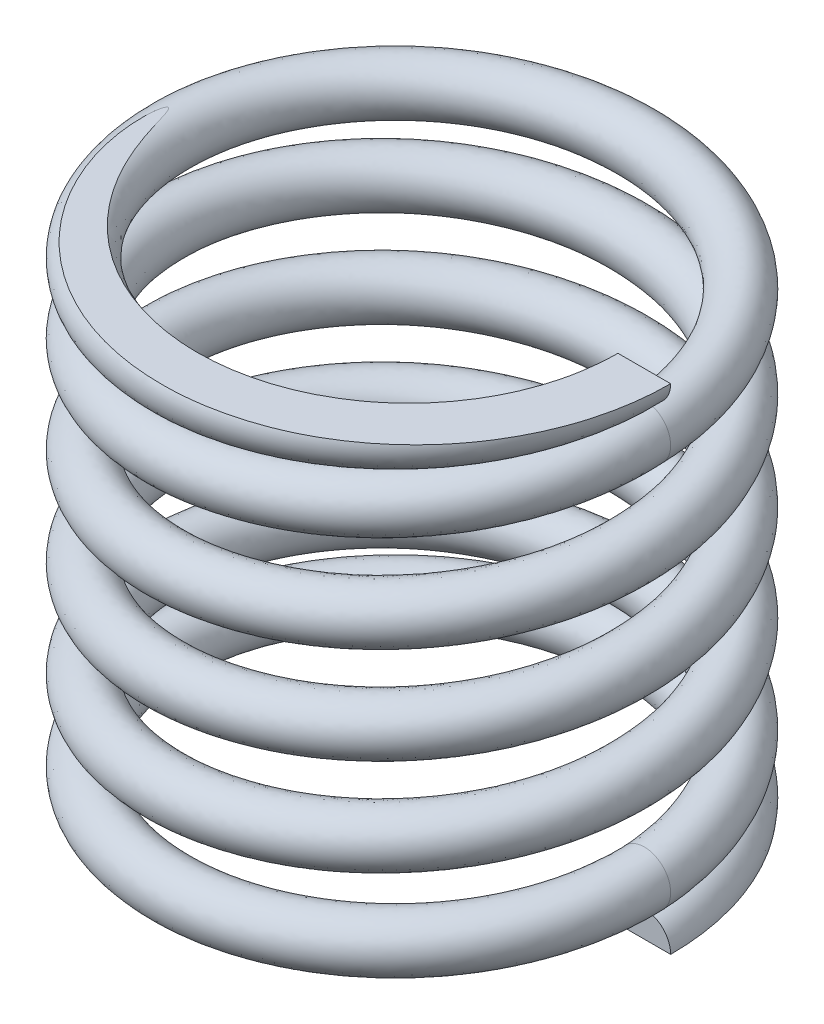
SolidWorks part; units mm, degrees
material "AISI Type 316L stainless steel"
ref_plane "Front" through (0, 0, 0) normal (0, 0, 1) x (1, 0, 0)
ref_plane "Top" through (0, 0, 0) normal (0, 1, 0) x (1, 0, 0)
ref_plane "Right" through (0, 0, 0) normal (1, 0, 0) x (0, 0, -1)
sketch "Sketch1" plane through (0, 0, 0) normal (0, 0, 1) x (1, 0, 0)
  line L0 (7.0499, 15) -> (7.0499, 14.1999) construction
  line L1 (0, 0) -> (7.0499, 0) construction
  line L2 (0, 0) -> (0, 15) construction
  line L3 (0, 15) -> (7.0499, 15) construction
  line L4 (7.0499, 14.1999) -> (7.0499, 14.1745) construction
  line L5 (7.0499, 14.1745) -> (7.0499, 12.5743) construction
  line L6 (7.0499, 12.5743) -> (7.0499, 2.4257) construction
  line L7 (7.0499, 2.4257) -> (7.0499, 0.8255) construction
  line L8 (7.0499, 0.8255) -> (7.0499, 0.8001) construction
  line L9 (7.0499, 0.8001) -> (7.0499, 0) construction
  line L10 (7.0499, 0) -> (7.85, 0) construction
  line L11 (7.0499, 1.6256) -> (7.85, 1.6256) construction
  line L12 (7.0499, 15) -> (7.85, 15) construction
  line L13 (7.0499, 15) -> (7.0499, 15.8001) construction
  line L14 (7.0499, 0) -> (7.0499, -0.8001) construction
  circle A0 centre (7.0499, 15) radius 0.8001 construction
  circle A1 centre (7.0499, 13.3744) radius 0.8001 construction
  circle A2 centre (7.0499, 1.6256) radius 0.8001
  circle A3 centre (7.0499, 0) radius 0.8001 construction
  dimension "Wire Dia" = 1.6002
  dimension "D3" = 11.7488
  dimension "D4" = 1.6256
  dimension "D1" = 0.0254
  dimension "Spring-OD" = 15.7
  dimension "Overall Height" = 15
ref_plane "Plane1" through (0, 1.6256, 0) normal (0, 1, 0) x (-1, 0, 0)
sketch "Sketch3" plane through (0, 1.6256, 0) normal (0, 1, 0) x (-1, 0, 0)
  circle A0 centre (0, 0) radius 7.85
curve "Helix1" pitch 2.9372 height 11.7488 turns 4
sweep "Sweep1" add profiles "Sketch1" path "Helix1"
sketch "Sketch4" plane through (0, 1.6256, 0) normal (0, 1, 0) x (-1, 0, 0)
  circle A0 centre (0, 0) radius 7.85 construction
  circle A1 centre (0, 0) radius 7.85
curve "Helix2" pitch 1.6256 height 1.6256 turns 1
sketch "Sketch5" plane through (0, 0, 0) normal (0, 0, 1) x (1, 0, 0)
  circle A0 centre (7.0499, 0) radius 0.8001 construction
  circle A1 centre (7.0499, 0) radius 0.8001
sweep "Sweep2" add profiles "Sketch5" path "Helix2"
ref_plane "Plane2" through (0, 13.3744, 0) normal (0, 1, 0) x (-1, 0, 0)
sketch "Sketch6" plane through (0, 13.3744, 0) normal (0, 1, 0) x (-1, 0, 0)
  circle A0 centre (0, 0) radius 7.85 construction
  circle A1 centre (0, 0) radius 7.85
curve "Helix3" pitch 1.6256 height 1.6256 turns 1
sketch "Sketch7" plane through (0, 0, 0) normal (0, 0, 1) x (1, 0, 0)
  circle A0 centre (7.0499, 13.3744) radius 0.8001 construction
  circle A1 centre (7.0499, 13.3744) radius 0.8001
sweep "Sweep3" add profiles "Sketch7" path "Helix3"
sketch "Sketch8" plane through (0, 0, 0) normal (0, 0, 1) x (1, 0, 0)
  line L0 (0, 0) -> (0, 15) construction
  line L1 (0, 15) -> (7.85, 15)
  line L2 (0, 15) -> (0, 15.8001)
  line L3 (0, 15.8001) -> (7.85, 15.8001)
  line L4 (7.85, 15) -> (7.85, 15.8001)
  line L5 (0, 0) -> (7.85, 0)
  line L6 (0, 0) -> (0, -0.8001)
  line L7 (0, -0.8001) -> (7.85, -0.8001)
  line L8 (7.85, 0) -> (7.85, -0.8001)
  line L9 (0, 0) -> (0, 15) construction
revolve "Cut-Revolve1" cut sketch "Sketch8" angle 360 about L9
equation "\"D3@Helix1\"=\"D3@Sketch1\""
equation "\"D3@Helix2\"=\"D4@Sketch1\""
equation "\"D3@Helix3\"=\"D4@Sketch1\""
